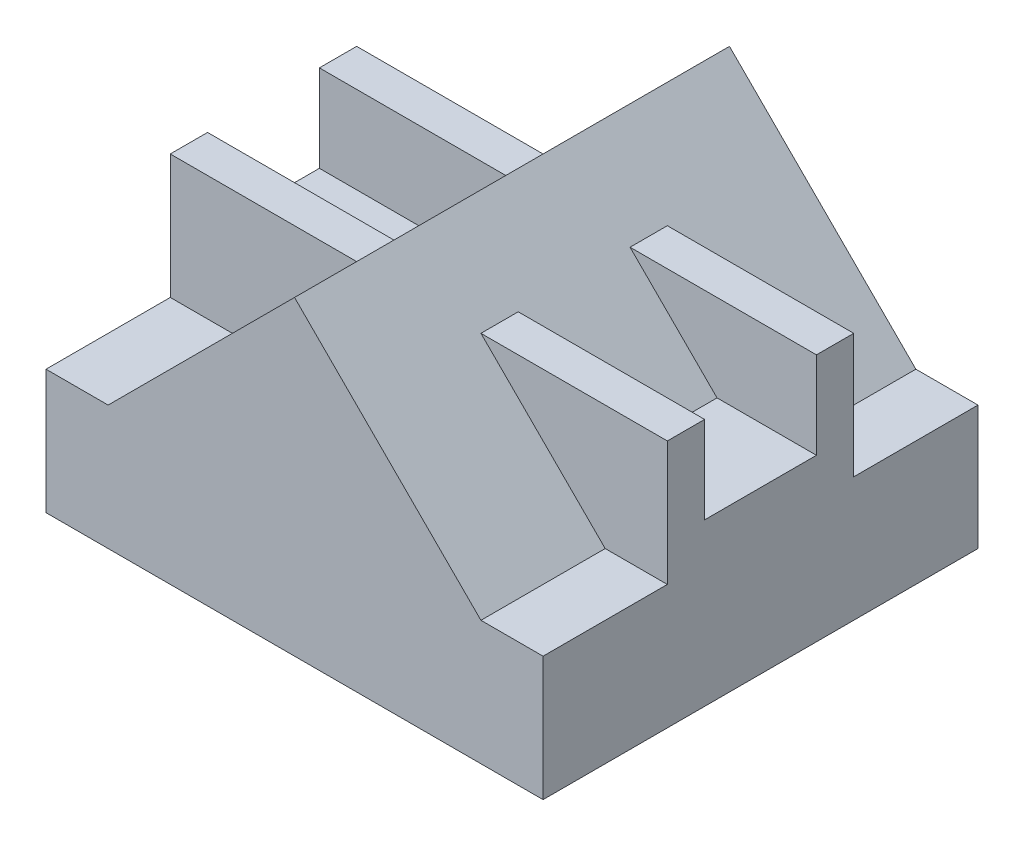
SolidWorks part; units mm, degrees
ref_plane "Front Plane" through (0, 0, 0) normal (0, 0, 1) x (1, 0, 0)
ref_plane "Top Plane" through (0, 0, 0) normal (0, 1, 0) x (1, 0, 0)
ref_plane "Right Plane" through (0, 0, 0) normal (1, 0, 0) x (0, 0, -1)
sketch "Sketch1" plane through (0, 0, 0) normal (0, 1, 0) x (1, 0, 0)
  line L6 (0, 0) -> (100, 0)
  line L7 (0, 0) -> (0, 87.5)
  line L8 (0, 87.5) -> (100, 87.5)
  line L9 (100, 0) -> (100, 87.5)
  line L10 (100, 50) -> (0, 50)
  line L11 (100, 50) -> (100, 65)
  line L12 (100, 65) -> (0, 65)
  line L13 (0, 50) -> (0, 65)
  dimension "D1" = 100
  dimension "D2" = 87.5
  dimension "D3" = 50
  dimension "D4" = 15
extrude "Boss-Extrude1" add sketch "Sketch1" along normal blind 50 contours L9 L10 L7 L6 | L9 L12 L7 L10 | L12 L9 L8 L7 region at (50, 0, -25) region at (50, 0, -57.5) region at (50, 0, -76.25)
extrude "Boss-Extrude2" add sketch "Sketch1<3>" along normal blind 100 contours L10 L13 L12 L11
sketch "Sketch1<3>" plane through (0, 0, 0) normal (0, 1, 0) x (1, 0, 0) same geometry as "Sketch1"
extrude "Boss-Extrude3" add sketch "Sketch1<4>" along normal blind 15 from surface contours L12 L9 L8 L7 region at (50, 0, -76.25) starting at face at (50, 50, -25)
sketch "Sketch1<4>" plane through (0, 0, 0) normal (0, 1, 0) x (1, 0, 0) same geometry as "Sketch1"
sketch "Sketch2" plane through (0, 0, 0) normal (0, 0, 1) x (1, 0, 0)
  line L0 (0, -48.125) -> (0, 48.125) construction
  line L2 (0, 125) -> (75, 50)
  line L3 (0, 50) -> (100, 50) construction
  line L4 (0, 125) -> (0, 50)
  line L5 (0, 50) -> (75, 50)
  point P0 (0, 125)
  dimension "D1" = 45
extrude "Boss-Extrude4" add sketch "Sketch2" against normal blind 87.5
mirror "Mirror1" about plane through (0, 50, -87.5) normal (0, 0, -1) of "Boss-Extrude1", "Boss-Extrude2", "Boss-Extrude3", "Boss-Extrude4"
mirror "Mirror10" about plane through (0, 50, 0) normal (-1, 0, 0) of bodies 105
